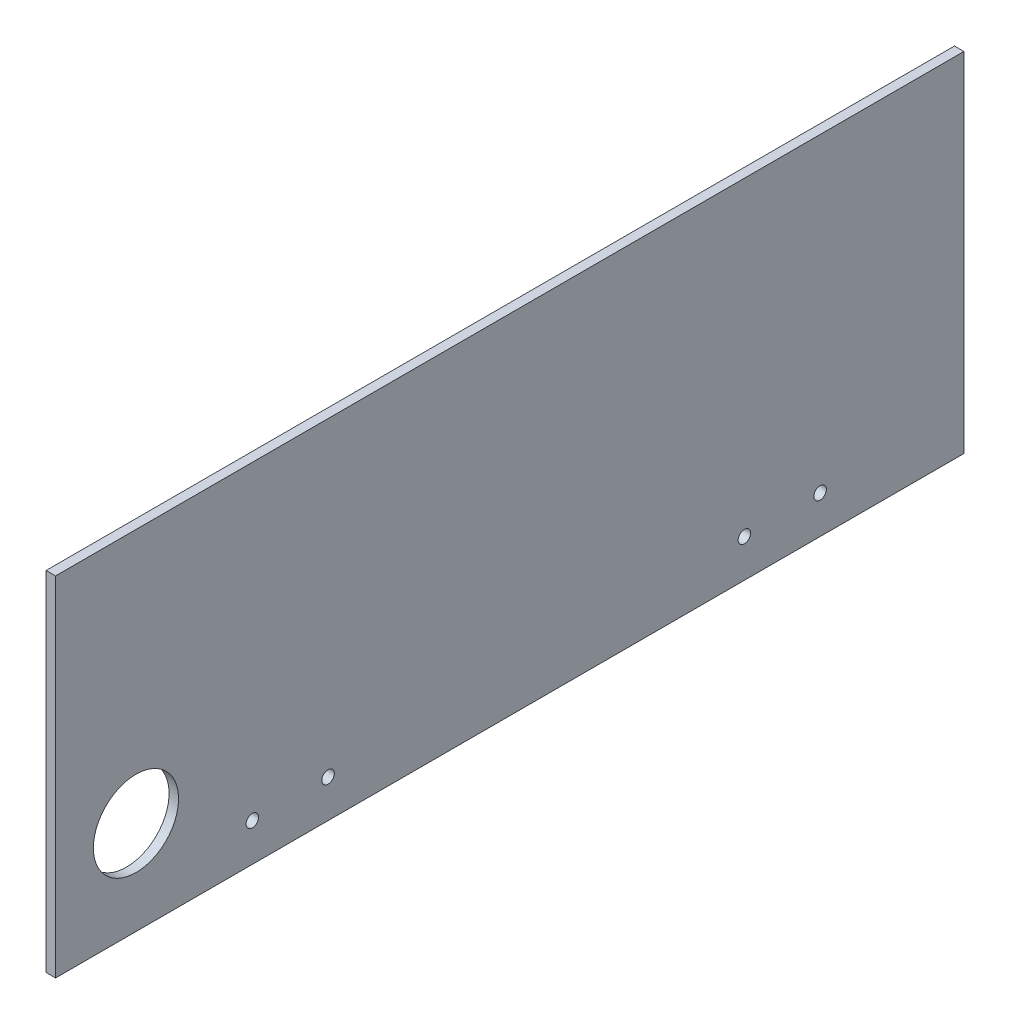
SolidWorks part; units mm, degrees
ref_plane "Front Plane" through (0, 0, 0) normal (0, 0, 1) x (1, 0, 0)
ref_plane "Top Plane" through (0, 0, 0) normal (0, 1, 0) x (1, 0, 0)
ref_plane "Right Plane" through (0, 0, 0) normal (1, 0, 0) x (0, 0, -1)
sketch "Sketch1" plane through (0, 0, 0) normal (1, 0, 0) x (0, 0, -1)
  line L1 (-152.4, -58.42) -> (152.4, -58.42)
  line L2 (-152.4, -58.42) -> (-152.4, 58.42)
  line L3 (-152.4, 58.42) -> (152.4, 58.42)
  line L4 (152.4, -58.42) -> (152.4, 58.42)
  line L5 (-152.4, -58.42) -> (152.4, 58.42) construction
  line L6 (-152.4, 58.42) -> (152.4, -58.42) construction
  point P0 (0, 0)
  dimension "D1" = 116.84
  dimension "D2" = 304.8
extrude "Boss-Extrude1" add sketch "Sketch1" along normal blind 3.175
sketch "Sketch2" plane through (3.175, 0, 0) normal (1, 0, 0) x (0, 0, -1)
  line L0 (-152.4, -58.42) -> (-86.36, -58.42)
  line L1 (-152.4, -58.42) -> (152.4, -58.42) construction
  line L2 (-86.36, -58.42) -> (-86.36, -45.72)
  line L3 (-86.36, -45.72) -> (-60.96, -45.72)
  circle A0 centre (-86.36, -45.72) radius 2.0955
  circle A1 centre (-60.96, -45.72) radius 2.0955
  circle A2 centre (104.14, -45.72) radius 2.0955
  circle A3 centre (78.74, -45.72) radius 2.0955
  dimension "D4" = 4.191
  dimension "D5" = 4.191
  dimension "D1" = 66.04
  dimension "D2" = 12.7
  dimension "D3" = 25.4
  dimension "D6" = 2
extrude "Cut-Extrude1" cut sketch "Sketch2" against normal up to surface (3.175 mm away) contours L3 A0 L2 | L2 A0 L3 | A1 | A2 | A3 region at (3.175, -45.4235, 86.6565) region at (3.175, -43.6838, 60.96) region at (3.175, -46.6094, 85.4706) region at (3.175, -45.72, -104.14) region at (3.175, -45.72, -78.74) up to face at (0, 0, 0)
sketch "Sketch3" plane through (0, 0, 0) normal (-1, 0, 0) x (0, 0, 1)
  line L0 (152.4, -58.42) -> (152.4, -26.9875)
  line L1 (152.4, 58.42) -> (152.4, -58.42) construction
  line L2 (152.4, -26.9875) -> (125.4125, -26.9875)
  circle A0 centre (125.4125, -26.9875) radius 14.2875
  dimension "D3" = 28.575
  dimension "D1" = 31.4325
  dimension "D2" = 26.9875
extrude "Cut-Extrude2" cut sketch "Sketch3" against normal blind 3.175 contours A0
